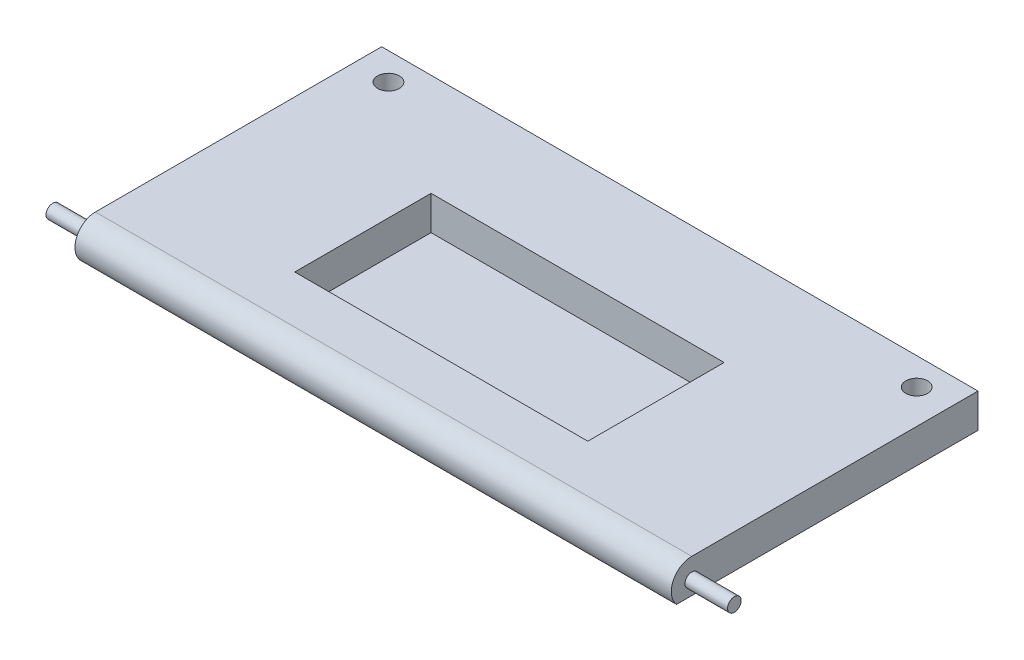
SolidWorks part; units mm, degrees
ref_plane "前视基准面" through (0, 0, 0) normal (0, 0, 1) x (1, 0, 0)
ref_plane "上视基准面" through (0, 0, 0) normal (0, 1, 0) x (1, 0, 0)
ref_plane "右视基准面" through (0, 0, 0) normal (1, 0, 0) x (0, 0, -1)
sketch "草图1" plane through (0, 0, 0) normal (0, 0, 1) x (1, 0, 0)
  line L0 (34, -2.5) -> (43.75, -2.5)
  line L1 (-43.75, -2.5) -> (-34, -2.5)
  line L2 (-43.75, -2.5) -> (-43.75, 2.5)
  line L3 (-43.75, 2.5) -> (43.75, 2.5)
  line L4 (43.75, -2.5) -> (43.75, 2.5)
  line L5 (-43.75, -2.5) -> (43.75, 2.5) construction
  line L6 (-43.75, 2.5) -> (43.75, -2.5) construction
  line L7 (-34, -3.5) -> (34, -3.5)
  line L8 (-34, -3.5) -> (-34, -2.5)
  line L10 (34, -3.5) -> (34, -2.5)
  line L11 (-34, -3.5) -> (34, -2.5) construction
  line L12 (-34, -2.5) -> (34, -3.5) construction
  point P0 (0, 0)
  point P6 (0, -3)
  dimension "D1" = 87.5
  dimension "D2" = 5
  dimension "D3" = 6
  dimension "D4" = 68
extrude "凸台-拉伸1" add sketch "草图1" along normal blind 45
sketch "草图2" plane through (0, 2.5, 0) normal (0, 1, 0) x (1, 0, 0)
  line L0 (43.75, 0) -> (-43.75, 0) construction
  line L1 (-21.5, -35) -> (21.5, -35)
  line L2 (-21.5, -35) -> (-21.5, -15)
  line L3 (-21.5, -15) -> (21.5, -15)
  line L4 (21.5, -35) -> (21.5, -15)
  line L5 (-21.5, -35) -> (21.5, -15) construction
  line L6 (-21.5, -15) -> (21.5, -35) construction
  point P0 (0, -25)
  dimension "D1" = 43
  dimension "D2" = 20
  dimension "D3" = 15
extrude "切除-拉伸2" cut sketch "草图2" against normal blind 5
fillet "圆角2" 2 edges at (0, 2.5, 45) (0, -3.5, 45) type full round first side face at (0, 2.5, 25) second side face at (0, -3.5, 22.5) middle face at (0, -1.5, 45)
sketch "草图4" plane through (-43.75, 0, 0) normal (-1, 0, 0) x (0, 0, 1)
  line L0 (0, 2.5) -> (0, -2.5) construction
  line L1 (42, 2.5) -> (0, 2.5) construction
  circle A0 centre (42, -0.5) radius 1
  point P3 (0, 0)
  dimension "D1" = 2
  dimension "D2" = 42
  dimension "D3" = 3
extrude "凸台-拉伸2" add sketch "草图4" along normal mid plane 100 from surface starting at plane "右视基准面"
sketch "草图5" plane through (0, -2.5, 0) normal (0, -1, 0) x (1, 0, 0)
  line L0 (-43.75, 0) -> (-34, 0) construction
  line L1 (-43.75, 44.2361) -> (-43.75, 0) construction
  circle A0 centre (-38.75, 4) radius 1.6
  dimension "D1" = 3.2
  dimension "D3" = 5
  dimension "D2" = 4
extrude "切除-拉伸3" cut sketch "草图5" against normal up to next
mirror "镜向1" about plane through (0, 0, 0) normal (1, 0, 0) of "切除-拉伸3"
